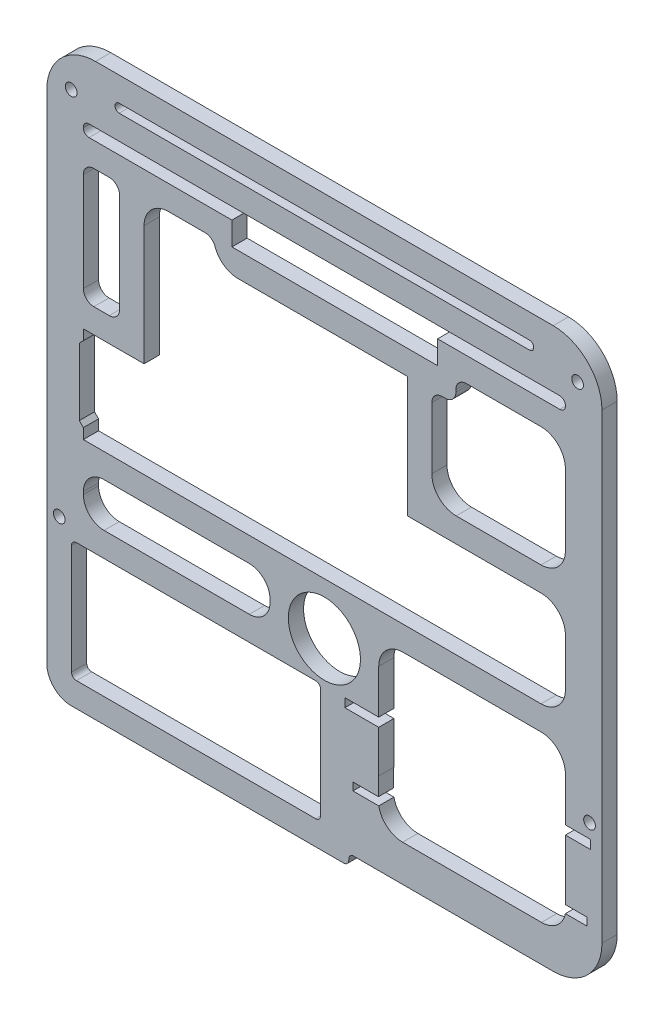
SolidWorks part; units mm, degrees
ref_plane "Front Plane" through (0, 0, 0) normal (0, 0, 1) x (1, 0, 0)
ref_plane "Top Plane" through (0, 0, 0) normal (0, 1, 0) x (1, 0, 0)
ref_plane "Right Plane" through (0, 0, 0) normal (1, 0, 0) x (0, 0, -1)
sketch "Sketch1" plane through (0, 0, 0) normal (0, 0, 1) x (1, 0, 0)
  line L0 (63.9883, 61.406) -> (63.9883, 57.596) construction
  line L1 (13.2322, 3.1158) -> (71.0996, 3.1158)
  line L2 (13.2322, 3.1158) -> (13.2322, 61.406)
  line L3 (13.2322, 61.406) -> (71.0996, 61.406)
  line L4 (71.0996, 3.1158) -> (71.0996, 61.406)
  line L5 (67.2896, 57.596) -> (17.0422, 57.596)
  line L6 (67.2896, 57.596) -> (67.2896, 6.9258)
  line L7 (67.2896, 6.9258) -> (17.0422, 6.9258)
  line L8 (17.0422, 57.596) -> (17.0422, 6.9258)
  line L9 (63.9883, 59.501) -> (18.0707, 59.501) construction
  line L10 (17.0422, 39.3805) -> (13.2322, 39.3805) construction
  line L11 (15.1372, 39.3805) -> (15.1372, 23.9527) construction
  line L12 (13.5248, 6.9258) -> (13.5248, 3.1158) construction
  line L13 (13.5248, 5.0208) -> (21.1598, 5.0208) construction
  line L14 (71.0996, 38.1916) -> (67.2896, 38.1916) construction
  line L15 (69.1946, 38.1916) -> (69.1946, 22.3321) construction
  line L16 (55.7422, 59.501) -> (30.5962, 59.501) construction
  line L17 (69.1946, 37.887) -> (69.1946, 50.1298) construction
  line L18 (15.1372, 26.6348) -> (15.1372, 14.392) construction
  line L19 (42.3087, 5.0208) -> (41.7626, 5.0208) construction
  dimension "D1" = 3.81
  dimension "D2" = 3.81
extrude "Boss-Extrude1" add sketch "Sketch1" along normal blind 1.5875
sketch "Sketch2" plane through (0, 0, 0) normal (0, 0, -1) x (-1, 0, 0)
  line L0 (-67.2896, 6.9258) -> (-67.2896, 57.596) construction
  line L1 (-67.2896, 26.6348) -> (-17.0422, 26.6348)
  line L2 (-67.2896, 26.6348) -> (-67.2896, 24.0948)
  line L3 (-67.2896, 24.0948) -> (-17.0422, 24.0948)
  line L4 (-17.0422, 26.6348) -> (-17.0422, 24.0948)
  line L5 (-17.0422, 57.596) -> (-17.0422, 6.9258) construction
  line L6 (-20.1206, 26.6348) -> (-57.8206, 26.6348) construction
  line L8 (-53.9642, 51.7667) -> (-53.9642, 54.1924) construction
  line L9 (-32.5266, 51.7667) -> (-53.9642, 51.7667) construction
  line L10 (-32.5266, 51.7667) -> (-32.5266, 54.1924) construction
  line L11 (-67.2896, 54.1924) -> (-53.9642, 54.1924)
  line L12 (-67.2896, 54.1924) -> (-67.2896, 51.6524)
  line L13 (-67.2896, 51.6524) -> (-55.8692, 51.6524)
  line L14 (-17.0422, 54.1924) -> (-17.0422, 51.6524)
  line L15 (-67.2896, 57.596) -> (-17.0422, 57.596)
  line L16 (-67.2896, 57.596) -> (-67.2896, 55.4243)
  line L17 (-67.2896, 55.4243) -> (-17.0422, 55.4243)
  line L18 (-17.0422, 57.596) -> (-17.0422, 55.4243)
  line L19 (-67.2896, 57.596) -> (-17.0422, 57.596) construction
  line L20 (-62.3462, 54.1924) -> (-23.9922, 54.1924) construction
  line L21 (-62.3462, 55.4243) -> (-23.9922, 55.4243) construction
  line L22 (-53.9642, 51.7667) -> (-53.9642, 54.1924)
  line L23 (-32.5266, 51.7667) -> (-53.9642, 51.7667)
  line L24 (-32.5266, 51.7667) -> (-32.5266, 54.1924)
  line L25 (-55.8692, 51.6524) -> (-55.8692, 49.2267)
  line L26 (-55.8692, 49.2267) -> (-30.6216, 49.2267)
  line L27 (-30.6216, 49.2267) -> (-30.6216, 51.6524)
  line L28 (-30.6216, 51.6524) -> (-17.0422, 51.6524)
  line L29 (-32.5266, 54.1924) -> (-17.0422, 54.1924)
  dimension "D1" = 2.54
  dimension "D2" = 1.905
  dimension "D3" = 2.54
  dimension "D4" = 1.905
extrude "Boss-Extrude2" add sketch "Sketch2" against normal up to surface (1.5875 mm away) up to face at (42.1659, 32.2609, 1.5875)
sketch "Sketch3" plane through (0, 0, 0) normal (0, 0, -1) x (-1, 0, 0)
  line L0 (-57.8206, 36.6348) -> (-50.8206, 36.6348) construction
  line L1 (-57.8206, 36.6348) -> (-50.8206, 36.6348)
  line L2 (-57.8206, 36.6348) -> (-67.2896, 36.6348)
  line L3 (-67.2896, 26.6348) -> (-67.2896, 51.6524) construction
  line L4 (-67.2896, 36.6348) -> (-67.2896, 39.1748)
  line L5 (-67.2896, 39.1748) -> (-53.3606, 39.1748)
  line L6 (-50.8206, 28.408) -> (-50.8206, 36.6348)
  line L7 (-50.8206, 28.408) -> (-50.8206, 49.2267)
  line L8 (-55.8692, 49.2267) -> (-30.6216, 49.2267) construction
  line L9 (-50.8206, 49.2267) -> (-53.3606, 49.2267)
  line L10 (-53.3606, 49.2267) -> (-53.3606, 39.1748)
  line L11 (-23.3706, 36.6348) -> (-20.1206, 36.6348) construction
  line L12 (-23.3706, 36.6348) -> (-20.1206, 36.6348)
  line L13 (-20.1206, 36.6348) -> (-17.0422, 36.6348)
  line L14 (-17.0422, 51.6524) -> (-17.0422, 26.6348) construction
  line L15 (-17.0422, 36.6348) -> (-17.0422, 39.1748)
  line L16 (-17.0422, 39.1748) -> (-20.8306, 39.1748)
  line L17 (-20.8306, 39.1748) -> (-20.8306, 51.6524)
  line L18 (-30.6216, 51.6524) -> (-17.0422, 51.6524) construction
  line L19 (-20.8306, 51.6524) -> (-23.3706, 51.6524)
  line L20 (-23.3706, 51.6524) -> (-23.3706, 36.6348)
  line L21 (-23.3706, 36.6348) -> (-16.2412, 25.8471)
  line M22 (-67.2896, 26.6348) -> (-67.2896, 51.6524)
  line M25 (-55.8692, 49.2267) -> (-30.6216, 49.2267)
  line M27 (-30.6216, 51.6524) -> (-17.0422, 51.6524)
  line M28 (-17.0422, 51.6524) -> (-17.0422, 26.6348)
  dimension "D1" = 2.54
  dimension "D2" = 2.54
  dimension "D3" = 2.54
  dimension "D4" = 2.54
extrude "Boss-Extrude3" add sketch "Sketch3" against normal up to surface (1.5875 mm away) contours L10 L5 L2 L1 L6 L7 M25 M22 | L20 L12 L13 L16 L17 M27 M28 region at (62.5551, 36.8422, 0) region at (21.4631, 42.8869, 0) up to face at (42.7056, 53.894, 1.5875)
sketch "Sketch4" plane through (0, 0, 0) normal (0, 0, -1) x (-1, 0, 0)
  line L0 (-67.2896, 24.0948) -> (-17.0422, 24.0948) construction
  line L1 (-47.8301, 24.0948) -> (-36.5017, 24.0948)
  line L2 (-47.8301, 24.0948) -> (-47.8301, 6.9258)
  line L3 (-47.8301, 6.9258) -> (-36.5017, 6.9258)
  line L4 (-36.5017, 24.0948) -> (-36.5017, 6.9258)
  line L5 (-17.0422, 6.9258) -> (-67.2896, 6.9258) construction
  line L6 (-45.9251, 21.2246) -> (-47.8301, 21.2246) construction
  line L7 (-38.4067, 21.2246) -> (-36.5017, 21.2246) construction
  circle A0 centre (-42.1659, 21.2246) radius 3.7592 construction
  dimension "D1" = 1.905
extrude "Boss-Extrude4" add sketch "Sketch4" against normal up to surface (1.5875 mm away) up to face at (18.9364, 45.4136, 1.5875)
sketch "Sketch5" plane through (0, 0, 0) normal (0, 0, -1) x (-1, 0, 0)
  line L0 (-15.8038, 16.9715) -> (-41.7626, 16.9715) construction
  line L3 (-41.7626, 4.5128) -> (-41.7626, 16.9715) construction
  line L4 (-15.8038, 4.5128) -> (-41.7626, 4.5128) construction
  line L5 (-15.8038, 4.5128) -> (-15.8038, 16.9715) construction
  line L6 (-15.8038, 16.9715) -> (-41.7626, 16.9715)
  line L7 (-41.7626, 4.5128) -> (-41.7626, 16.9715)
  line L8 (-15.8038, 4.5128) -> (-41.7626, 4.5128)
  line L9 (-15.8038, 4.5128) -> (-15.8038, 16.9715)
  circle A0 centre (-42.1659, 21.2246) radius 3.7592 construction
  circle A1 centre (-42.1659, 21.2246) radius 3.7592
extrude "Cut-Extrude1" cut sketch "Sketch5" against normal up to surface (1.5875 mm away) up to face at (57.5598, 15.5103, 1.5875)
sketch "Sketch8" plane through (0, 0, 0) normal (0, 0, -1) x (-1, 0, 0)
  line L0 (-17.0422, 24.0948) -> (-17.0422, 16.9715) construction
  line L1 (-36.5017, 16.9715) -> (-17.0422, 16.9715)
  line L2 (-36.5017, 16.9715) -> (-36.5017, 19.5115)
  line L3 (-36.5017, 19.5115) -> (-17.0422, 19.5115)
  line L4 (-17.0422, 16.9715) -> (-17.0422, 19.5115)
  dimension "D1" = 2.54
extrude "Boss-Extrude5" add sketch "Sketch8" against normal up to surface (1.5875 mm away) up to face at (38.4067, 21.2246, 1.5875)
fillet "Fillet1" radius 5.08 3 edges at (71.0996, 3.1158, 0.7937) (13.2322, 61.406, 0.7937) (71.0996, 61.406, 0.7937)
fillet "Fillet2" radius 2.54 7 edges at (23.3706, 51.6524, 0.7937) (30.6216, 49.2267, 0.7937) (67.2896, 51.6524, 0.7937) (53.3606, 39.1748, 0.7938) (67.2896, 26.6348, 0.7937) (67.2896, 39.1748, 0.7937) (67.2896, 36.6348, 0.7937)
fillet "Fillet3" radius 1.0922 8 edges at (53.3606, 49.2267, 0.7937) (55.8692, 49.2267, 0.7937) (55.8692, 51.6524, 0.7937) (17.0422, 39.1748, 0.7937) (20.8306, 39.1748, 0.7937) (17.0422, 51.6524, 0.7937) (20.8306, 51.6524, 0.7937) (30.6216, 51.6524, 0.7937)
fillet "Fillet4" radius 0.5842 4 edges at (17.0422, 54.1924, 0.7937) (17.0422, 55.4243, 0.7937) (67.2896, 55.4243, 0.7937) (67.2896, 54.1924, 0.7937)
fillet "Fillet8" radius 2.159 4 edges at (36.5017, 19.5115, 0.7937) (36.5017, 24.0948, 0.7937) (17.0422, 24.0948, 0.7937) (17.0422, 19.5115, 0.7937)
sketch "Sketch6" plane through (0, 0, 0) normal (0, 0, -1) x (-1, 0, 0)
  line L0 (-16.6206, 28.1348) -> (-18.1206, 26.6348) construction
  line L1 (-18.1206, 36.6348) -> (-16.6206, 35.1348) construction
  line L2 (-16.6206, 35.1348) -> (-16.6206, 28.1348) construction
  line L3 (-16.6206, 28.1348) -> (-18.1206, 26.6348)
  line L4 (-18.1206, 36.6348) -> (-16.6206, 35.1348)
  line L5 (-16.6206, 35.1348) -> (-16.6206, 28.1348)
  line L6 (-18.1206, 36.6348) -> (-18.1206, 26.6348)
  circle A4 centre (-68.5596, 57.596) radius 0.6096 construction
  circle A5 centre (-68.5596, 57.596) radius 0.6096
  circle A6 centre (-14.5276, 18.4306) radius 0.6096 construction
  circle A7 centre (-14.5276, 18.4306) radius 0.6096
  circle A8 centre (-69.8042, 18.4306) radius 0.6096 construction
  circle A9 centre (-69.8042, 18.4306) radius 0.6096
  circle A10 centre (-15.7722, 57.596) radius 0.6096 construction
  circle A11 centre (-15.7722, 57.596) radius 0.6096
extrude "Cut-Extrude2" cut sketch "Sketch6" against normal up to surface (1.5875 mm away) up to face at (28.7832, 10.7422, 1.5875)
sketch "Sketch7" plane through (0, 0, 0) normal (0, 0, -1) x (-1, 0, 0)
  line L0 (-44.3026, 16.9715) -> (-69.8804, 16.9715) construction
  line L1 (-69.8804, 16.9715) -> (-69.8804, 16.0571) construction
  line L2 (-69.8804, 16.0571) -> (-44.3026, 16.0571) construction
  line L3 (-44.3026, 16.0571) -> (-44.3026, 16.9715) construction
  line L4 (-45.1366, 9.7751) -> (-69.5206, 9.7751) construction
  line L5 (-69.5206, 9.7751) -> (-69.5206, 8.9623) construction
  line L6 (-69.5206, 8.9623) -> (-45.1366, 8.9623) construction
  line L7 (-45.1366, 8.9623) -> (-45.1366, 9.7751) construction
  line L8 (-44.3026, 16.9715) -> (-69.8804, 16.9715)
  line L9 (-69.8804, 16.9715) -> (-69.8804, 16.0571)
  line L10 (-69.8804, 16.0571) -> (-44.3026, 16.0571)
  line L11 (-44.3026, 16.0571) -> (-44.3026, 16.9715)
  line L12 (-45.1366, 9.7751) -> (-69.5206, 9.7751)
  line L13 (-69.5206, 9.7751) -> (-69.5206, 8.9623)
  line L14 (-69.5206, 8.9623) -> (-45.1366, 8.9623)
  line L15 (-45.1366, 8.9623) -> (-45.1366, 9.7751)
  line L20 (-66.8536, 9.7751) -> (-47.8036, 9.7751)
  line L21 (-47.8036, 9.7751) -> (-47.8036, 11.6547)
  line L22 (-47.8036, 11.6547) -> (-66.8536, 11.6547)
  line L23 (-66.8536, 11.6547) -> (-66.8536, 9.7751)
  line L24 (-66.8536, 9.7751) -> (-47.8036, 9.7751)
  line L25 (-47.8036, 9.7751) -> (-47.8036, 11.6547)
  line L26 (-47.8036, 11.6547) -> (-66.8536, 11.6547)
  line L27 (-66.8536, 11.6547) -> (-66.8536, 9.7751)
  dimension "D1" = 0
extrude "Cut-Extrude3" cut sketch "Sketch7" against normal up to surface (1.5875 mm away) contours L14 L15 L12 L13 | L26 L27 L12 L25 | L10 L11 L8 L9 region at (57.0915, 16.5143, 0) region at (57.3286, 9.3687, 0) region at (57.3286, 10.7149, 0) up to face at (15.1626, 57.596, 1.5875)
fillet "Fillet6" radius 0.508 4 edges at (41.7626, 16.9715, 0.7937) (41.7626, 4.5128, 0.7937) (15.8038, 4.5128, 0.7937) (15.8038, 16.9715, 0.7937)
sketch "Sketch9" plane through (0, 0, 1.5875) normal (0, 0, 1) x (1, 0, 0)
  line L0 (66.0196, 61.406) -> (18.3122, 61.406) construction
  line L1 (20.3442, 58.866) -> (63.9876, 58.866)
  line L2 (20.3442, 58.866) -> (20.3442, 57.9643)
  line L3 (20.3442, 57.9643) -> (63.9876, 57.9643)
  line L8 (63.9876, 58.866) -> (63.9876, 57.9643)
  line L9 (17.6264, 55.4243) -> (66.7054, 55.4243) construction
  line L10 (13.2322, 56.326) -> (13.2322, 59.3208) construction
  line L11 (20.3442, 58.866) -> (13.2322, 58.866) construction
  line L13 (63.9876, 58.866) -> (71.0996, 58.866) construction
  line L14 (71.0996, 56.326) -> (71.0996, 56.8419) construction
  dimension "D1" = 2.54
  dimension "D2" = 2.54
  dimension "D3" = 7.112
extrude "Cut-Extrude4" cut sketch "Sketch9" against normal up to surface (1.5875 mm away) up to face at (56.5457, 13.2916, 0)
fillet "Fillet7" radius 0.4318 4 edges at (20.3442, 57.9643, 0.7937) (20.3442, 58.866, 0.7937) (63.9876, 57.9643, 0.7937) (63.9876, 58.866, 0.7937)
fillet "Fillet9" radius 2.54 4 edges at (67.2896, 6.9258, 0.7937) (47.8301, 6.9258, 0.7937) (67.2896, 24.0948, 0.7937) (47.8301, 24.0948, 0.7937)
sketch "Sketch10" plane through (0, 0, 1.5875) normal (0, 0, 1) x (1, 0, 0)
  line L0 (42.1659, 24.9838) -> (42.1659, -13.4858) construction
  line L1 (13.2322, 3.1158) -> (44.7059, 3.1158)
  line L2 (13.2322, 3.1158) -> (13.2322, 1.9728)
  line L3 (13.2322, 1.9728) -> (44.7059, 1.9728)
  line L4 (44.7059, 3.1158) -> (44.7059, 1.9728)
  line L5 (16.3118, 4.5128) -> (41.2546, 4.5128) construction
  circle A0 centre (42.1659, 21.2246) radius 3.7592 construction
  dimension "D1" = 2.54
  dimension "D2" = 2.54
extrude "Boss-Extrude6" add sketch "Sketch10" against normal up to surface (1.5875 mm away) up to face at (42.1659, 58.4152, 0)
fillet "Fillet10" radius 2.54 1 edges at (13.2322, 1.9728, 0.7937)
fillet "Fillet11" radius 0.508 2 edges at (44.7059, 3.1158, 0.7937) (44.7059, 1.9728, 0.7937)
